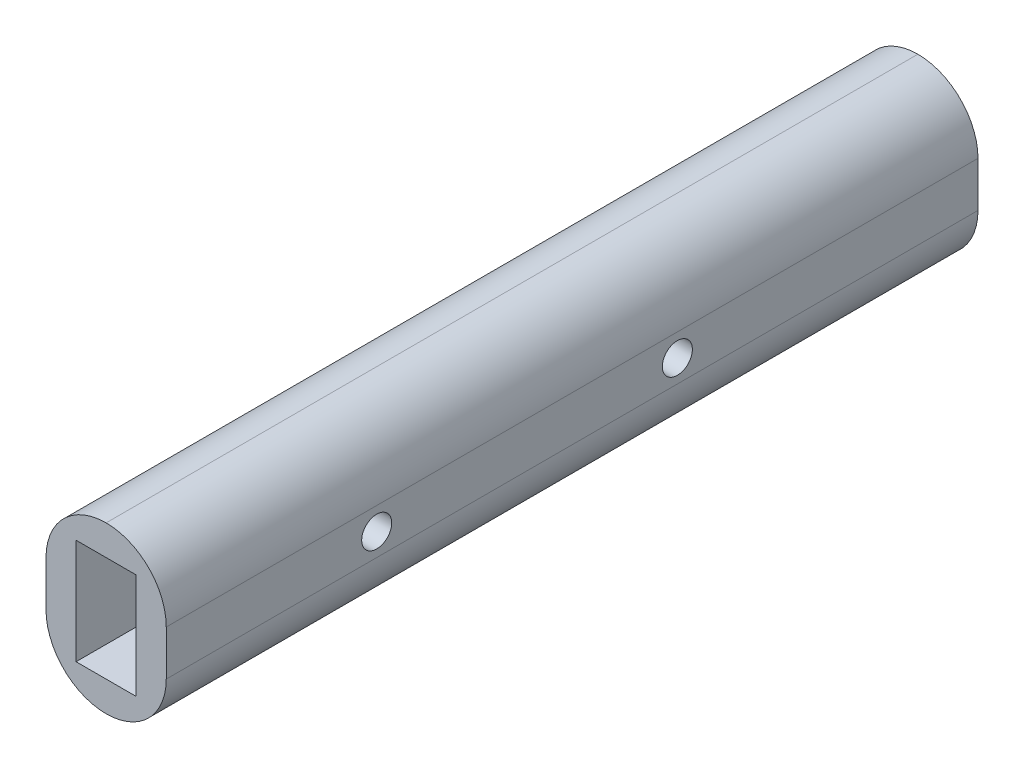
SolidWorks part; units mm, degrees
ref_plane "Front Plane" through (0, 0, 0) normal (0, 0, 1) x (1, 0, 0)
ref_plane "Top Plane" through (0, 0, 0) normal (0, 1, 0) x (1, 0, 0)
ref_plane "Right Plane" through (0, 0, 0) normal (1, 0, 0) x (0, 0, -1)
sketch "Sketch2" plane through (0, 0, 0) normal (0, 0, 1) x (1, 0, 0)
  line L0 (0, 0) -> (40, 0)
  line L1 (0, 0) -> (0, 55)
  line L2 (0, 55) -> (40, 55)
  line L3 (40, 55) -> (40, 0)
  dimension "D1" = 40
  dimension "D2" = 55
extrude "Boss-Extrude1" add sketch "Sketch2" along normal blind 270
sketch "Sketch3" plane through (0, 0, 0) normal (0, 0, -1) x (-1, 0, 0)
  line L0 (-30, 10) -> (-30, 45)
  line L1 (-30, 45) -> (-10, 45)
  line L2 (-10, 45) -> (-10, 10)
  line L3 (-10, 10) -> (-30, 10)
  dimension "D1" = 35
  dimension "D2" = 20
  dimension "D3" = 10
  dimension "D4" = 10
extrude "Cut-Extrude1" cut sketch "Sketch3" against normal through all
hole_wizard "Ø10.0mm Dowel Hole1" positions "Sketch4" profile "Sketch5" hole size "Ø10.0" standard "ANSI Metric" end condition through all
sketch "Sketch4" plane through (0, 0, 0) normal (-1, 0, 0) x (0, 0, 1)
  point P0 (200, 27.5)
  point P2 (100, 27.5)
  dimension "D1" = 100
  dimension "D2" = 100
  dimension "D3" = 27.5
  dimension "D4" = 27.5
sketch "Sketch5" plane through (0, 27.5, 200) normal (0, 1, 0) x (0, 0, 1)
  line L0 (0, 0) -> (0, 40)
  line L1 (0, 40) -> (5, 40)
  line L2 (5, 40) -> (5, 0)
  line L5 (5, 0) -> (0, 0)
  line L11 (0, -6.35) -> (0, 107.95) construction
  dimension "Thru Hole Dia." = 10
  dimension "Thru Hole Depth" = 40
fillet "Fillet2" radius 20 4 edges at (40, 0, 135) (0, 0, 135) (40, 55, 135) (0, 55, 135)
